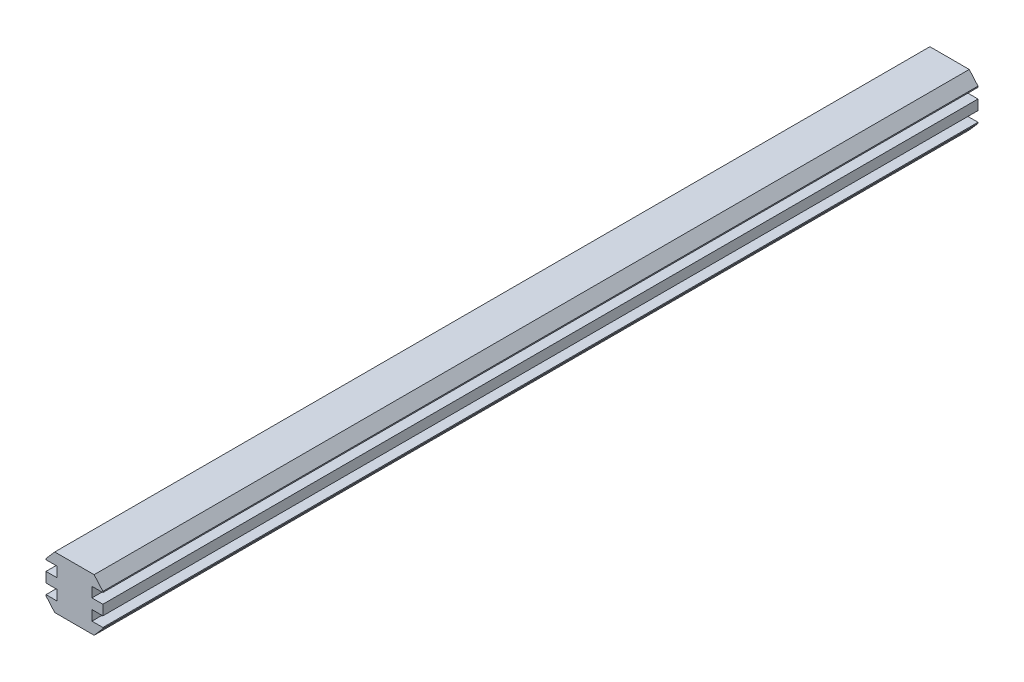
SolidWorks part; units mm, degrees
material "PE Alta Densidade"
ref_plane "Plano frontal" through (0, 0, 0) normal (0, 0, 1) x (1, 0, 0)
ref_plane "Plano superior" through (0, 0, 0) normal (0, 1, 0) x (1, 0, 0)
ref_plane "Plano direito" through (0, 0, 0) normal (1, 0, 0) x (0, 0, -1)
sketch "Esboço1" plane through (0, 0, 0) normal (0, 0, 1) x (1, 0, 0)
  line L0 (-4.5, -6) -> (4.5, -6)
  line L1 (-4.5, -6) -> (-6.5, -3.7)
  line L2 (6.5, -3.7) -> (6.5, -3.45)
  line L3 (6.5, -3.45) -> (4, -3.45)
  line L4 (4, -3.45) -> (4, -1.15)
  line L5 (4, -1.15) -> (6.5, -1.15)
  line L6 (6.5, -1.15) -> (6.5, 1.15)
  line L7 (4, 1.15) -> (6.5, 1.15)
  line L8 (4, 3.45) -> (4, 1.15)
  line L9 (6.5, 3.45) -> (4, 3.45)
  line L10 (6.5, 3.7) -> (6.5, 3.45)
  line L11 (4.5, -6) -> (6.5, -3.7)
  line L12 (4.5, 6) -> (6.5, 3.7)
  line L13 (0, 14.388) -> (0, -9.624) construction
  line L14 (-4.5, 6) -> (4.5, 6)
  line L15 (-6.5, -3.7) -> (-6.5, -3.45)
  line L16 (-6.5, -3.45) -> (-4, -3.45)
  line L17 (-4, -3.45) -> (-4, -1.15)
  line L18 (-4, -1.15) -> (-6.5, -1.15)
  line L19 (-6.5, -1.15) -> (-6.5, 1.15)
  line L20 (-4.5, 6) -> (-6.5, 3.7)
  line L21 (-6.5, 3.7) -> (-6.5, 3.45)
  line L22 (-6.5, 3.45) -> (-4, 3.45)
  line L23 (-4, 3.45) -> (-4, 1.15)
  line L24 (-4, 1.15) -> (-6.5, 1.15)
  line L25 (-8.8286, 0) -> (11.4625, 0) construction
  point P0 (0, 0)
  point P1 (6.5, -6)
  point P17 (-6.5, -6)
  point P31 (6.5, 0)
  point P33 (0, -6)
  dimension "D1" = 12
  dimension "D2" = 13
  dimension "D3" = 2.3
  dimension "D4" = 2.3
  dimension "D5" = 0.25
  dimension "D6" = 8
  dimension "D7" = 9
extrude "Ressalto-extrusão1" add sketch "Esboço1" along normal blind 200
